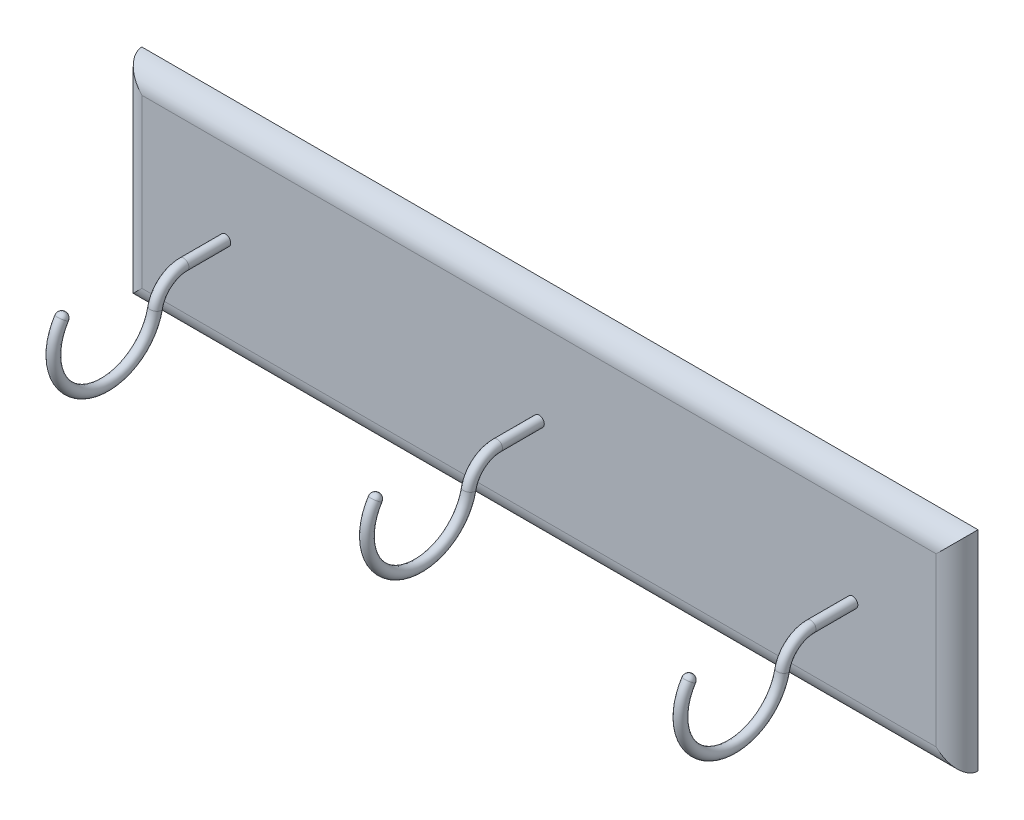
SolidWorks part; units mm, degrees
ref_plane "Alzado" through (0, 0, 0) normal (0, 0, 1) x (1, 0, 0)
ref_plane "Planta" through (0, 0, 0) normal (0, 1, 0) x (1, 0, 0)
ref_plane "Vista lateral" through (0, 0, 0) normal (1, 0, 0) x (0, 0, -1)
sketch "Croquis1" plane through (0, 0, 0) normal (0, 0, 1) x (1, 0, 0)
  line L1 (-200, -50) -> (200, -50)
  line L2 (-200, -50) -> (-200, 50)
  line L3 (-200, 50) -> (200, 50)
  line L4 (200, -50) -> (200, 50)
  line L5 (-200, -50) -> (200, 50) construction
  line L6 (-200, 50) -> (200, -50) construction
  point P0 (0, 0)
  dimension "D1" = 100
  dimension "D2" = 400
extrude "Saliente-Extruir1" add sketch "Croquis1" along normal blind 10
fillet "Redondeo1" radius 10 4 edges at (0, -50, 10) (-200, 0, 10) (0, 50, 10) (200, 0, 10)
sketch "Croquis2" plane through (0, 0, 10) normal (0, 0, 1) x (1, 0, 0)
  circle A0 centre (0, 0) radius 2.5
  dimension "D1" = 5
sketch "Croquis3" plane through (0, 0, 0) normal (1, 0, 0) x (0, 0, -1)
  line L0 (-10, 0) -> (-30, 0)
  line L1 (-10, 2.5) -> (-10, -2.5) construction
  arc A0 (-30, 0) -> (-43.6673, -11.2306) centre (-30, -13.9317) ccw
  arc A1 (-43.6673, -11.2306) -> (-88.3717, 6.9492) centre (-67.7783, -6.4656) cw
  dimension "D3" = 20
sweep "Barrer1" add profiles "Croquis2" path "Croquis3"
dome "Cúpula1" faces to dome 1 distance 2.5 reverse direction no elliptical dome no face at (2.5, 6.9492, 88.3717) parameters "D1"=2.5
pattern_linear "MatrizL3" count 2 spacing 150 along (1, 0, 0) of "Barrer1", "Cúpula1"
pattern_linear "MatrizL4" count 2 spacing 150 along (-1, 0, 0) of "Cúpula1", "Barrer1"
